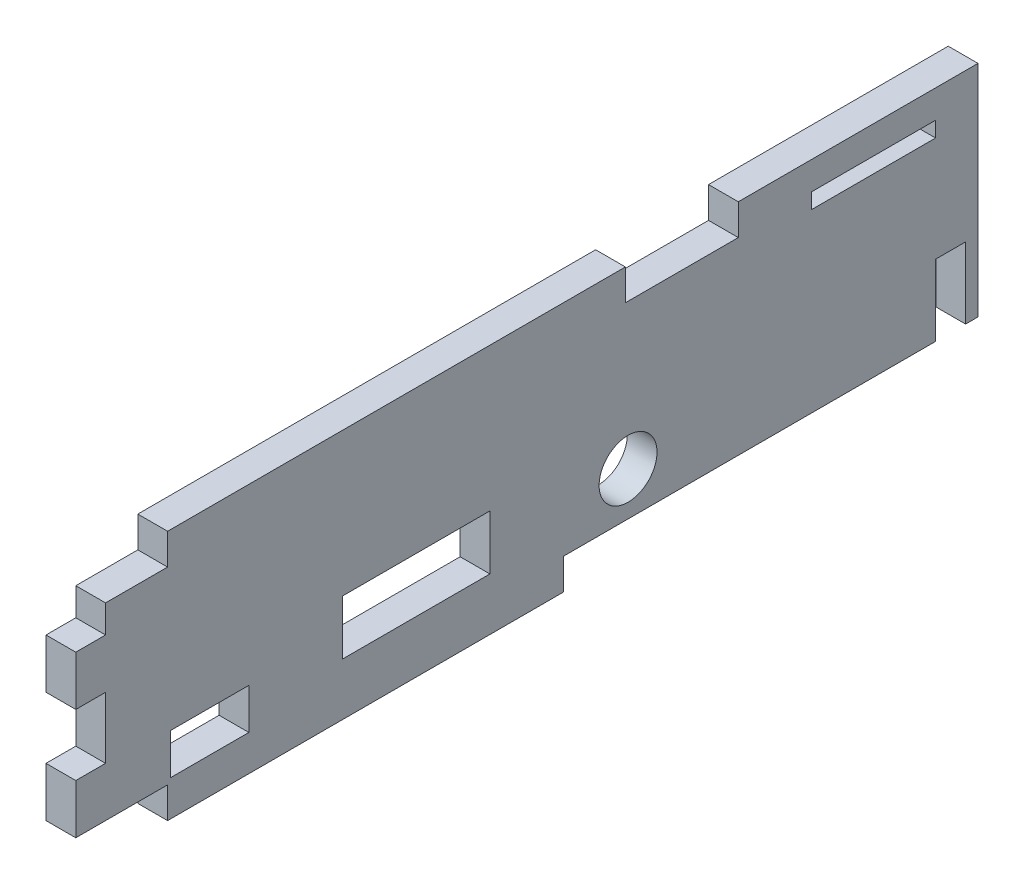
SolidWorks part; units mm, degrees
ref_plane "Front" through (0, 0, 0) normal (0, 0, 1) x (1, 0, 0)
ref_plane "Top" through (0, 0, 0) normal (0, 1, 0) x (1, 0, 0)
ref_plane "Right" through (0, 0, 0) normal (1, 0, 0) x (0, 0, -1)
sketch "Sketch2" plane through (0, 0, 0) normal (1, 0, 0) x (0, 0, -1)
  line L0 (0, 4.7244) -> (84.963, 4.7244) construction
  line L1 (0, 24.0284) -> (84.963, 24.0284)
  line L2 (0, 24.0284) -> (0, 0)
  line L3 (0, 0) -> (84.963, 0)
  line L4 (84.963, 24.0284) -> (84.963, 0)
  line L5 (6.6294, 9.3853) -> (14.6685, 9.3853)
  line L6 (6.6294, 9.3853) -> (6.6294, 5.207)
  line L7 (6.6294, 5.207) -> (14.6685, 5.207)
  line L8 (14.6685, 9.3853) -> (14.6685, 5.207)
  line L9 (24.257, 6.9215) -> (39.3446, 6.9215)
  line L10 (24.257, 6.9215) -> (24.257, 12.5095)
  line L11 (24.257, 12.5095) -> (39.3446, 12.5095)
  line L12 (39.3446, 6.9215) -> (39.3446, 12.5095)
  line L13 (53.486, 12.1412) -> (53.486, 4.7244) construction
  line L14 (6.35, 24.0284) -> (6.35, 27.2034)
  line L15 (6.35, 27.2034) -> (53.213, 27.2034)
  line L16 (84.963, 24.0284) -> (86.7664, 24.0284)
  line L17 (6.35, 4.7244) -> (6.35, 1.5494)
  line L18 (6.35, 1.5494) -> (46.863, 1.5494)
  line L19 (46.863, 1.5494) -> (46.863, 4.7244)
  line L20 (46.863, 4.7244) -> (84.963, 4.7244)
  line L21 (6.35, 4.7244) -> (0, 4.7244)
  line L22 (86.7664, 24.0284) -> (86.7664, 4.7244)
  line L23 (86.7664, 24.0284) -> (89.3064, 24.0284)
  line L24 (89.3064, 24.0284) -> (89.3064, 4.7244)
  line L25 (84.963, 12.0142) -> (86.7664, 12.0142)
  line L26 (86.7664, 4.7244) -> (89.3064, 4.7244)
  line L27 (84.963, 22.7584) -> (72.263, 22.7584)
  line L28 (42.4815, 24.0284) -> (42.4815, 0) construction
  line L29 (-3.048, 4.7244) -> (0, 4.7244)
  line L30 (-3.048, 9.8044) -> (-3.048, 4.7244)
  line L31 (-3.048, 9.8044) -> (0, 9.8044)
  line L32 (-3.048, 16.1036) -> (0, 16.1036)
  line L33 (-3.048, 21.1836) -> (-3.048, 16.1036)
  line L34 (0, 21.1836) -> (-3.048, 21.1836)
  line L35 (53.213, 27.2034) -> (53.213, 24.0284)
  line L36 (72.263, 22.7584) -> (72.263, 24.5618)
  line L37 (72.263, 24.5618) -> (84.963, 24.5618)
  line L38 (84.963, 24.5618) -> (84.963, 24.0284)
  line L39 (89.3064, 24.0284) -> (89.3064, 27.2034)
  line L40 (89.3064, 27.2034) -> (64.77, 27.2034)
  line L41 (64.77, 27.2034) -> (64.77, 24.0284)
  circle A0 centre (53.486, 9.1758) radius 2.9655
  dimension "D11" = 5.9309
  dimension "D13" = 11.176
  dimension "D1" = 84.963
  dimension "D2" = 8.0391
  dimension "D3" = 15.0876
  dimension "D4" = 4.6609
  dimension "D5" = 4.1783
  dimension "D6" = 6.6294
  dimension "D7" = 7.7851
  dimension "D8" = 5.588
  dimension "D9" = 9.5885
  dimension "D10" = 4.7244
  dimension "D12" = 7.4168
  dimension "D14" = 19.304
  dimension "D15" = 6.35
  dimension "D16" = 3.175
  dimension "D17" = 3.175
  dimension "D18" = 38.1
  dimension "D19" = 3.048
  dimension "D20" = 2.8448
  dimension "D21" = 5.08
  dimension "D22" = 5.08
  dimension "D23" = 31.75
  dimension "D24" = 1.8034
  dimension "D25" = 1.27
  dimension "D26" = 12.7
extrude "Boss-Extrude1" add sketch "Sketch2" along normal blind 3.048 contours L21 L17 L18 L19 L20 L4 L1 L2 A0 L12 L9 L10 L11 L5 L8 L7 L6 | L23 L4 | L4 | L15 L14 L1 | L2 L34 L33 L32 | L31 L30 L29 L2 | L22 L26 L24 L23 | L40 L41 L1 L36 L37 L38 L16 L23 L39 region at (0, 13.8682, -41.8848) region at (0, 25.6159, -29.7815) region at (0, 18.6436, 1.524) region at (0, 25.7417, -76.8882) region at (0, 7.2644, 1.524) region at (0, 18.0213, -85.8647) region at (0, 14.3764, -88.0364)
sketch "Sketch3" plane through (0, 0, 0) normal (-1, 0, 0) x (0, 0, 1)
  line L0 (-72.263, 22.7584) -> (-72.263, 24.5618) construction
  line L1 (-84.963, 24.5618) -> (-72.263, 24.5618)
  line L2 (-84.963, 24.5618) -> (-84.963, 24.3332)
  line L3 (-84.963, 24.3332) -> (-72.263, 24.3332)
  line L4 (-72.263, 24.5618) -> (-72.263, 24.3332)
  line L5 (-84.963, 22.7584) -> (-72.263, 22.7584) construction
  dimension "D1" = 1.5748
extrude "made hood slot smaller" add sketch "Sketch3" against normal up to vertex (3.048 mm away) up to point (3.048, 27.2034, -64.77)
sketch "Sketch4" plane through (3.048, 0, 0) normal (1, 0, 0) x (0, 0, -1)
  line B0 (6.6294, 5.207) -> (14.6685, 5.207)
  line B1 (24.257, 6.9215) -> (39.3446, 6.9215)
  line B2 (14.6685, 9.3853) -> (14.6685, 5.207)
  line B3 (6.6294, 9.3853) -> (14.6685, 9.3853)
  line B4 (6.6294, 9.3853) -> (6.6294, 5.207)
  line B5 (24.257, 6.9215) -> (24.257, 12.5095)
  line B6 (24.257, 12.5095) -> (39.3446, 12.5095)
  line B7 (39.3446, 6.9215) -> (39.3446, 12.5095)
  line B8 (46.863, 4.7244) -> (84.963, 4.7244)
  line B9 (0, 16.1036) -> (0, 9.8044)
  circle B10 centre (53.486, 9.1758) radius 2.9655
sketch_block_instance "Block1-1"
sketch_block "Block1"
sketch "Sketch5" plane through (3.048, 0, 0) normal (1, 0, 0) x (0, 0, -1)
  line L0 (86.7664, 4.7244) -> (89.3064, 4.7244) construction
  line L1 (84.963, 12.0142) -> (88.0364, 12.0142)
  line L2 (84.963, 12.0142) -> (84.963, 4.7244)
  line L3 (84.963, 4.7244) -> (88.0364, 4.7244)
  line L4 (88.0364, 12.0142) -> (88.0364, 4.7244)
extrude "Cut-Extrude1" cut sketch "Sketch5" against normal through all
